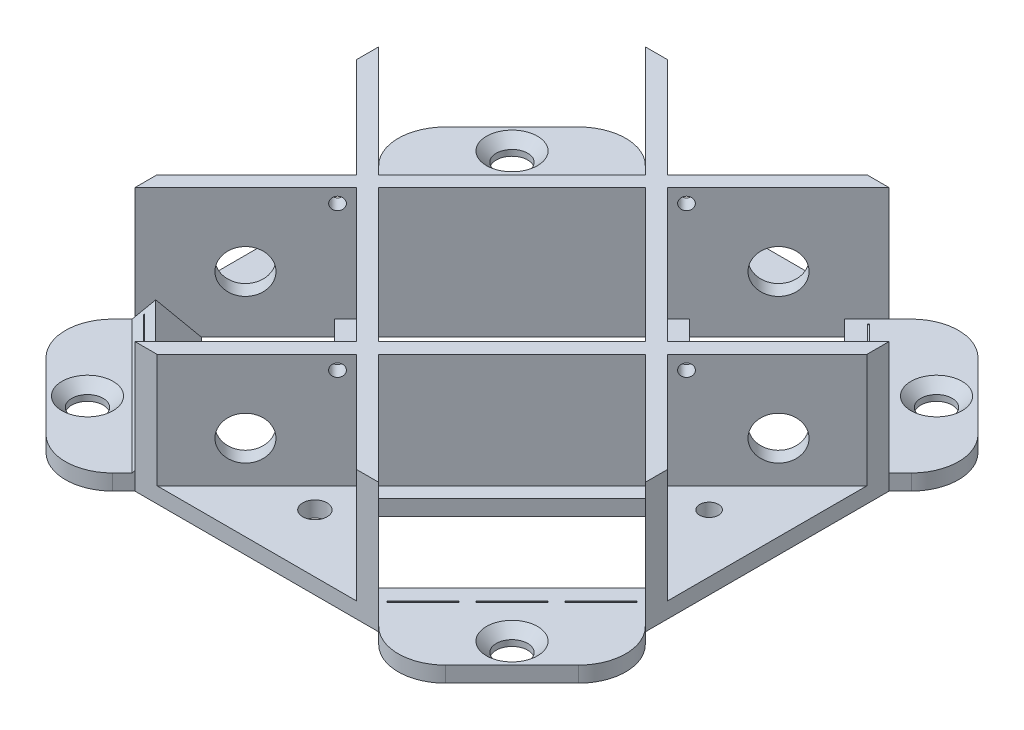
SolidWorks part; units mm, degrees
material "Windform GT"
ref_plane "Front Plane" through (0, 0, 0) normal (0, 0, 1) x (1, 0, 0)
ref_plane "Top Plane" through (0, 0, 0) normal (0, 1, 0) x (1, 0, 0)
ref_plane "Right Plane" through (0, 0, 0) normal (1, 0, 0) x (0, 0, -1)
ref_axis "Axis1" through (0, 2.1, 0) along (0, -1, 0)
sketch "Usable Space" plane through (0, 0, 0) normal (0, 1, 0) x (1, 0, 0)
  line L1 (-32.5, -32.5) -> (32.5, -32.5) construction
  line L2 (-32.5, -32.5) -> (-32.5, 32.5) construction
  line L3 (-32.5, 32.5) -> (32.5, 32.5) construction
  line L4 (32.5, -32.5) -> (32.5, 32.5) construction
  line L5 (-32.5, -32.5) -> (32.5, 32.5) construction
  line L6 (-32.5, 32.5) -> (32.5, -32.5) construction
  point P0 (0, 0)
  dimension "D1" = 65
sketch "Sketch3" plane through (0, 0, 0) normal (0, 1, 0) x (1, 0, 0)
  line L0 (-32.5, -12.701) -> (-12.701, -32.5)
  line L1 (-32.5, -32.5) -> (-32.5, 32.5) construction
  line L2 (-12.701, -32.5) -> (0, -19.799)
  line L3 (-32.5, -32.5) -> (32.5, 32.5) construction
  line L4 (0, -19.799) -> (0, 0)
  line L5 (0, 0) -> (-19.799, 0)
  line L7 (-19.799, 0) -> (-32.5, -12.701)
  line L8 (-32.5, -32.5) -> (32.5, -32.5) construction
  dimension "D1" = 28
extrude "General shape" add sketch "Sketch3" along normal blind 2
sketch "Sketch4" plane through (0, 2, 0) normal (0, 1, 0) x (1, 0, 0)
  line L0 (-19.799, 0) -> (-32.5, -12.701)
  line L1 (-19.799, 0) -> (-32.5, -12.701) construction
  line L2 (-32.5, -12.701) -> (-31.0858, -14.1152)
  line L3 (-31.0858, -14.1152) -> (-16.9706, 0)
  line L4 (0, 0) -> (-19.799, 0) construction
  line L5 (-16.9706, 0) -> (-19.799, 0)
  line L6 (-22.6005, -22.6005) -> (0, 0) construction
  line L7 (-32.5, -12.701) -> (-12.701, -32.5) construction
  line L8 (-14.1152, -31.0858) -> (0, -16.9706)
  line L9 (-12.701, -32.5) -> (-14.1152, -31.0858)
  line L10 (0, -19.799) -> (-12.701, -32.5)
  line L11 (0, -16.9706) -> (0, -19.799)
  dimension "D1" = 2
extrude "Retaining walls" add sketch "Sketch4" along normal blind 14.5
sketch "Sketch14" plane through (0, 0, 0) normal (0, -1, 0) x (1, 0, 0)
  line L0 (-19.799, 0) -> (-32.5, 12.701)
  line L1 (-19.799, 0) -> (-32.5, 12.701) construction
  line L2 (-32.5, 12.701) -> (-32.5, 0)
  line L3 (-32.5, 0) -> (-19.799, 0)
  line L4 (0, 19.799) -> (0, 32.5)
  line L5 (0, 32.5) -> (-12.701, 32.5)
  line L6 (-12.701, 32.5) -> (0, 19.799) construction
  line L7 (0, 19.799) -> (-12.701, 32.5)
  circle A1 centre (-29.049, 0) radius 1 construction
  dimension "D1" = 9.25
  dimension "D2" = 2
extrude "Exterior mounting edge" add sketch "Sketch14" against normal blind 2
sketch "Sketch18" plane through (0, 2, 0) normal (0, 1, 0) x (1, 0, 0)
  line L0 (-16.9706, 0) -> (0, -16.9706)
  line L1 (-18.3848, -1.4142) -> (-1.4142, -18.3848)
  line L2 (-31.0858, -14.1152) -> (-16.9706, 0) construction
  line L3 (0, -16.9706) -> (-14.1152, -31.0858) construction
  line L4 (-18.3848, -1.4142) -> (-16.9706, 0)
  line L5 (0, -16.9706) -> (-1.4142, -18.3848)
  dimension "D1" = 2
extrude "Rear wall" add sketch "Sketch18" along normal blind 14.5
sketch "Sketch19" plane through (-8.4853, 0, 8.4853) normal (0.7071, 0, -0.7071) x (-0.7071, 0, -0.7071)
  line L0 (0, 16.5) -> (0, 2) construction
  line L1 (-12, 16.5) -> (12, 16.5) construction
  line L2 (-12, 2) -> (12, 2) construction
  point P6 (0, 9.25)
fillet "Fillet13" [suppressed] radius 1
ref_plane "Plane2" [suppressed] through (0, 0, 0) normal (0.7071, 0, 0.7071) x (0.7071, 0, -0.7071)
sketch "Sketch35" plane through (-9.8995, 0, -9.8995) normal (-0.7071, 0, -0.7071) x (-0.7071, 0, 0.7071)
  line L0 (24, 16.5) -> (24, 2) construction
  line L2 (14, 16.5) -> (14, 2) construction
  line L3 (14, 2) -> (31.9619, 2) construction
  line L4 (15.7119, 16.5) -> (15.7119, 2) construction
  line L5 (14, 16.5) -> (31.9619, 16.5) construction
  line L6 (14, 2) -> (31.9619, 2) construction
  line L7 (14, 16.5) -> (31.9619, 16.5) construction
  line L8 (31.9619, 16.5) -> (31.9619, 2) construction
  circle A0 centre (24, 7.25) radius 2.75
  circle A1 centre (15.7119, 14.75) radius 0.8
  point P14 (0, 0)
  point P17 (24.3129, 7.25)
  dimension "D1" = 5.5
  dimension "D4" = 1.6
  dimension "D5" = 1.75
  dimension "D6" = 9.25
  dimension "D2" = 10
  dimension "D3" = 16.25
extrude "Cut-Extrude2" cut sketch "Sketch35" against normal through all both and the other way through all
pattern_circular "CirPattern2" count 4 over 360 about axis through (0, 2.1, 0) along (0, -1, 0) of "General shape", "Retaining walls"
combine bodies "Combine1" operation type add bodies to combine 104 111 110 139
sketch "Exterior mounting hole location" plane through (0, 2, 0) normal (0, 1, 0) x (1, 0, 0)
  line L0 (-32.5, 0) -> (-19.799, 0) construction
  line L1 (-32.5, -12.701) -> (-32.5, 12.701) construction
  point P5 (-25.1, 0)
  point P7 (0, 25.1)
  point P13 (25.1, 0)
  point P14 (0, -25.1)
  dimension "D1" = 4
  dimension "D2" = 25.1
hole_wizard "Exterior mounting hole" positions "Sketch16" profile "Sketch17" hole size "M2" standard "ANSI Metric" end condition up to next
sketch "Sketch16" plane through (0, 2, 0) normal (0, 1, 0) x (1, 0, 0)
  point P0 (-25.1, 0)
  point P15 (25.1, 0)
sketch "Sketch17" plane through (-25.1, 2, 0) normal (1, 0, 0) x (0, 0, 1)
  line L0 (0, 0) -> (0, 2)
  line L1 (0, 2) -> (1.2, 2)
  line L2 (1.2, 2) -> (1.2, 0)
  line L5 (1.2, 0) -> (0, 0)
  line L11 (0, -6.35) -> (0, 107.95) construction
  dimension "Thru Hole Dia." = 2.4
  dimension "Thru Hole Depth" = 2
hole_wizard "Shoulder screw mounting holes " positions "Sketch24" profile "Sketch25" hole size "M2.5" standard "ANSI Metric" end condition up to next
sketch "Sketch24" plane through (0, 2, 0) normal (0, 1, 0) x (1, 0, 0)
  point P0 (0, -25.1)
  point P3 (0, 25.1)
sketch "Sketch25" plane through (0, 2, 25.1) normal (1, 0, 0) x (0, 0, 1)
  line L0 (0, 0) -> (0, 2)
  line L1 (0, 2) -> (1.55, 2)
  line L2 (1.55, 2) -> (1.55, 0)
  line L5 (1.55, 0) -> (0, 0)
  line L11 (0, -6.35) -> (0, 107.95) construction
  dimension "Thru Hole Dia." = 3.1
  dimension "Thru Hole Depth" = 2
sketch "Sketch23" plane through (0, 2, 0) normal (0, 1, 0) x (1, 0, 0)
  line L0 (0, 16.9706) -> (-16.9706, 0)
  line L5 (-16.9706, 0) -> (0, -16.9706)
  line L6 (0, -16.9706) -> (16.9706, 0)
  line L7 (16.9706, 0) -> (0, 16.9706)
  line L8 (31.0858, 14.1152) -> (18.3848, 1.4142) construction
  line L9 (18.3848, 1.4142) -> (1.4142, 18.3848) construction
  line L10 (1.4142, 18.3848) -> (14.1152, 31.0858) construction
  line L11 (-18.3848, 1.4142) -> (-31.0858, 14.1152) construction
  line L12 (-1.4142, 18.3848) -> (-18.3848, 1.4142) construction
  line L13 (-14.1152, 31.0858) -> (-1.4142, 18.3848) construction
  line L14 (-1.4142, -18.3848) -> (-14.1152, -31.0858) construction
  line L15 (-18.3848, -1.4142) -> (-1.4142, -18.3848) construction
  line L16 (-31.0858, -14.1152) -> (-18.3848, -1.4142) construction
  line L17 (14.1152, -31.0858) -> (1.4142, -18.3848) construction
  line L18 (18.3848, -1.4142) -> (31.0858, -14.1152) construction
  line L19 (1.4142, -18.3848) -> (18.3848, -1.4142) construction
  line L20 (31.0858, 14.1152) -> (18.3848, 1.4142)
  line L21 (18.3848, 1.4142) -> (1.4142, 18.3848)
  line L22 (1.4142, 18.3848) -> (14.1152, 31.0858)
  line L23 (-18.3848, 1.4142) -> (-31.0858, 14.1152)
  line L24 (-1.4142, 18.3848) -> (-18.3848, 1.4142)
  line L25 (-14.1152, 31.0858) -> (-1.4142, 18.3848)
  line L26 (-1.4142, -18.3848) -> (-14.1152, -31.0858)
  line L27 (-18.3848, -1.4142) -> (-1.4142, -18.3848)
  line L28 (-31.0858, -14.1152) -> (-18.3848, -1.4142)
  line L29 (14.1152, -31.0858) -> (1.4142, -18.3848)
  line L30 (18.3848, -1.4142) -> (31.0858, -14.1152)
  line L31 (1.4142, -18.3848) -> (18.3848, -1.4142)
  line L32 (-14.1152, 31.0858) -> (-31.0858, 14.1152)
  line L33 (-14.1152, -31.0858) -> (-31.0858, -14.1152)
  line L34 (14.1152, -31.0858) -> (31.0858, -14.1152)
  line L35 (31.0858, 14.1152) -> (14.1152, 31.0858)
extrude "Cut-Extrude1" cut sketch "Sketch23" against normal up to next
sketch "Sketch36" plane through (0, 0, 0) normal (0, 1, 0) x (1, 0, 0)
  line L6 (-12.701, -32.5) -> (-15.5294, -32.5)
  line L7 (-15.5294, -32.5) -> (-21.1863, -38.1569)
  line L8 (-21.1863, -38.1569) -> (-38.1569, -21.1863)
  line L16 (-38.1569, -21.1863) -> (-32.5, -15.5294)
  line L17 (-32.5, -12.701) -> (-31.0858, -14.1152)
  line L18 (-32.5, -15.5294) -> (-32.5, -12.701)
  line L19 (-32.5, -12.701) -> (-32.5, 12.701) construction
  line L20 (12.701, -32.5) -> (-12.701, -32.5) construction
  line L22 (-1.4142, -18.3848) -> (-14.1152, -31.0858) construction
  line L23 (-31.0858, -14.1152) -> (-18.3848, -1.4142) construction
  line L24 (-31.0858, -14.1152) -> (-29.6716, -12.701)
  line L25 (-12.701, -29.6716) -> (-14.1152, -31.0858)
  line L26 (-29.6716, -12.701) -> (-12.701, -29.6716)
  line L27 (-14.1152, -31.0858) -> (-12.701, -32.5)
  line L28 (-18.3848, -1.4142) -> (-1.4142, -18.3848) construction
  line L29 (-1.4142, -18.3848) -> (-2.8284, -19.799)
  line L30 (-18.3848, -1.4142) -> (-1.4142, -18.3848)
  line L31 (-31.0858, -14.1152) -> (-29.6716, -12.701)
  line L32 (-19.799, -2.8284) -> (-2.8284, -19.799)
  line L33 (-19.799, -2.8284) -> (-18.3848, -1.4142)
  line L34 (-12.701, -29.6716) -> (-14.1152, -31.0858)
  point P2 (-21.3984, -37.9447)
  point P3 (-38.0955, -21.2477)
  point P8 (-37.6075, -20.637)
  point P13 (-20.6931, -37.6637)
  point P22 (0, 0)
  dimension "D1" = 10
  dimension "D2" = 2
  dimension "D3" = 2
extrude "Boss-Extrude2" add sketch "Sketch36" along normal up to surface (2 mm away) contours L27 L25 L26 L24 L17 L18 L16 L8 L7 L6 | L32 L29 L30 L33 region at (-25.3966, 0, 25.3966) up to face at (0, 2, 26.65)
sketch "Sketch37" plane through (-8.4853, 0, -8.4853) normal (0.7071, 0, 0.7071) x (0.7071, 0, -0.7071)
  line L0 (-32.0833, 4.1213) -> (-29.9619, 2)
  line L1 (-34.2046, 2) -> (-29.9619, 2)
  line L2 (-29.9619, 2) -> (-27.9619, 0)
  line L4 (-33.9619, 2) -> (-41.9619, 2) construction
  line L5 (-32.0833, 4.1213) -> (-34.2046, 2)
  line L6 (-27.9619, 0) -> (-29.9619, 0)
  line L7 (-29.9619, 0) -> (-29.9619, 2)
  line L8 (-14, 0) -> (-33.9619, 0) construction
  point P7 (0, 0)
  point P8 (0, 0)
  point P15 (0, 0)
  point P16 (0, 0)
  point P17 (0, 0)
  line M17 (-31.9619, 16.5) -> (-31.9619, 2)
  line M18 (-31.9619, 2) -> (-29.9619, 2)
  line M19 (-29.9619, 2) -> (-29.9619, 0)
  line M20 (-29.9619, 0) -> (-16, 0)
  dimension "D2" = 45
  dimension "D3" = 3
extrude "Boss-Extrude3" add sketch "Sketch37" along normal up to surface (24 mm away) contours L0 L5 L1 | L0 M17 M18 | L2 M19 M20 region at (-29.2002, 0.6667, 12.2296) region at (-31.6173, 2.7395, 14.6468) region at (-30.6144, 2.6667, 13.6438) up to face at (-6.5407, 7.25, 23.5113)
sketch "Sketch40" plane through (-12.8003, 18.1023, 12.8003) normal (-0.5, 0.7071, 0.5) x (0.866, 0.4082, 0.2887)
  line L0 (-21.4295, -10.8203) -> (-3.0583, -23.8107)
  line L1 (-3.0583, -23.8107) -> (-3.1334, -23.9168)
  line L2 (-3.1334, -23.9168) -> (-21.5046, -10.9265)
  line L3 (-21.5046, -10.9265) -> (-21.4295, -10.8203)
  line L5 (-3.3495, -25.5215) -> (-22.9454, -11.6651) construction
  line L7 (-1.6175, -23.072) -> (-3.3495, -25.5215) construction
  line L8 (-22.0794, -10.4404) -> (-2.4835, -24.2968) construction
  line L9 (-1.6175, -23.072) -> (-3.3495, -25.5215) construction
  line L10 (-16.1223, -14.5731) -> (-16.1973, -14.6792)
  line L11 (-14.8975, -15.4391) -> (-14.9726, -15.5453)
  line L12 (-8.3656, -20.0579) -> (-8.4406, -20.1641)
  line L13 (-9.5903, -19.1919) -> (-9.6654, -19.298)
  line L16 (-1.6175, -23.072) -> (-21.2134, -9.2156) construction
  line L18 (-11.4154, -16.1438) -> (-13.1475, -18.5933) construction
  line L20 (-3.3495, -25.5215) -> (-22.9454, -11.6651) construction
  point P9 (0, 0)
  point P18 (-2.4835, -24.2968)
  point P19 (0, 0)
  point P30 (0, 0)
  point P33 (-13.1475, -18.5933)
  point P34 (0, 0)
  point P45 (-11.4154, -16.1438)
  dimension "D1" = 0.065
  dimension "D2" = 0.065
  dimension "D3" = 6.5
  dimension "D4" = 1.5
  dimension "D5" = 1.5
  dimension "D6" = 6.5
  dimension "D7" = 3.25
  dimension "D8" = 6.5
extrude "Cut-Extrude3" cut sketch "Sketch40" against normal up to surface (4.3934 mm away) contours L0 L12 L2 L1 | L13 L0 L11 L2 | L10 L0 L3 L2 region at (-29.0931, 3.0607, 17.7794) region at (-23.4363, 3.0607, 23.4363) region at (-17.7794, 3.0607, 29.0931) up to face at (-15.5429, 0, 15.5429)
sketch "Sketch41" plane through (0, 2, 0) normal (0, 1, 0) x (1, 0, 0)
  line L13 (-12.701, -32.5) -> (-15.5294, -32.5) construction
  line L14 (-14.1152, -31.0858) -> (-12.701, -32.5) construction
  line L15 (-12.701, -32.5) -> (-15.5294, -32.5)
  line L16 (-14.1152, -31.0858) -> (-12.701, -32.5)
  line L17 (-32.5, -12.701) -> (-31.0858, -14.1152) construction
  line L18 (-32.5, -15.5294) -> (-32.5, -12.701) construction
  line L19 (-32.5, -12.701) -> (-31.0858, -14.1152)
  line L20 (-32.5, -15.5294) -> (-32.5, -12.701)
  line L21 (-31.0858, -14.1152) -> (-32.5, -15.5294)
  line L23 (-15.5294, -32.5) -> (-14.1152, -31.0858)
  point P3 (0, 0)
  point P4 (0, 0)
  point P9 (0, 0)
  point P10 (0, 0)
  point P11 (0, 0)
  point P12 (0, 0)
extrude "Boss-Extrude4" add sketch "Sketch41" along normal up to surface (14.5 mm away) up to face at (0, 16.5, 0)
fillet "Fillet14" radius 6 2 edges at (-38.1569, 1, 21.1863) (-21.1863, 1, 38.1569)
sketch "Sketch42" plane through (0, 2, 0) normal (0, 1, 0) x (1, 0, 0)
  circle A1 centre (-27.0307, -27.0307) radius 2.653 construction
  circle A2 centre (-27.0307, -27.0307) radius 2.653 construction
  circle A3 centre (-27.0307, -27.0307) radius 2
  point P5 (0, 0)
  dimension "D1" = 4
extrude "Cut-Extrude4" cut sketch "Sketch42" against normal through all
chamfer "Chamfer1" distance 1.25 angle 45 1 edges at (-27.0307, 2, 29.0307)
pattern_circular "CirPattern15" count 4 over 360 about axis through (0, 2.1, 0) along (0, -1, 0) of "Boss-Extrude2", "Cut-Extrude3", "Fillet14", "Cut-Extrude4", "Boss-Extrude4", "Chamfer1"
